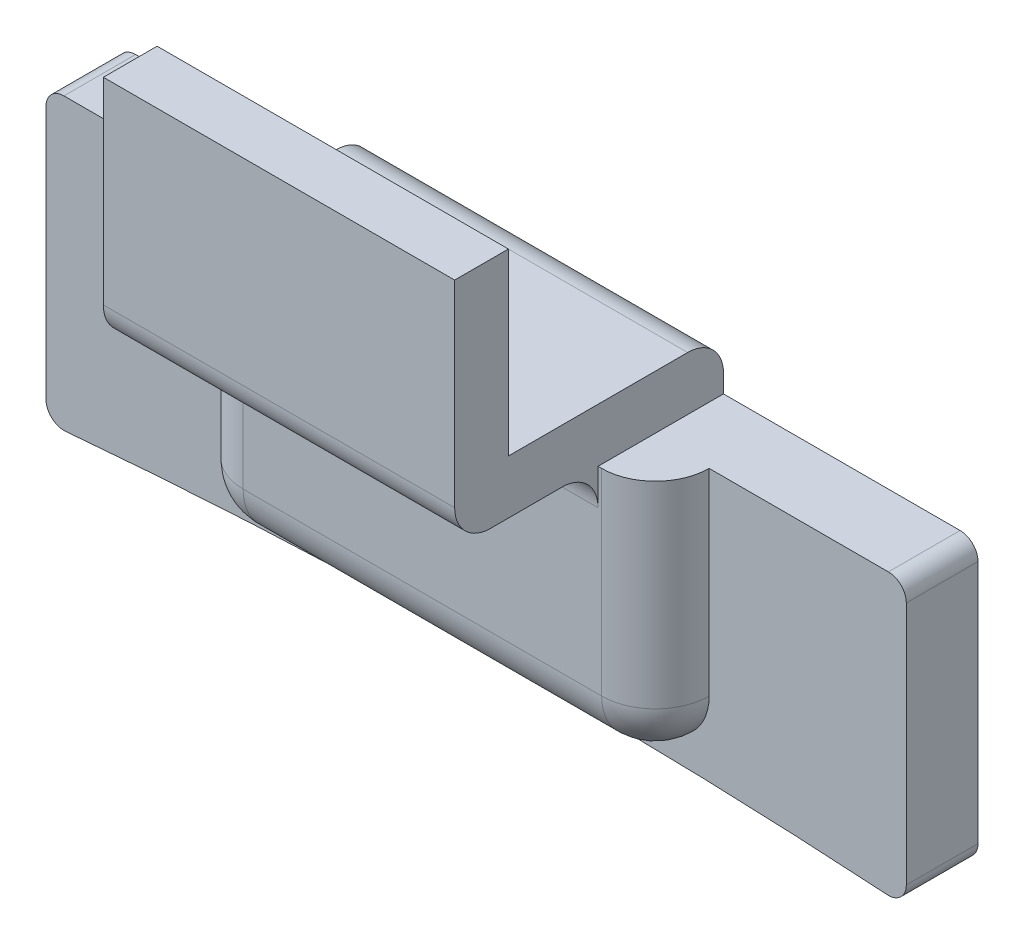
SolidWorks part; units mm, degrees
material "7079 Alloy"
ref_plane "Front Plane" through (0, 0, 0) normal (0, 0, 1) x (1, 0, 0)
ref_plane "Top Plane" through (0, 0, 0) normal (0, 1, 0) x (1, 0, 0)
ref_plane "Right Plane" through (0, 0, 0) normal (1, 0, 0) x (0, 0, -1)
ref_plane "Plane1" through (0, 0, 0) normal (0, 0, -1) x (-1, 0, 0)
sketch "Sketch1" plane through (0, 0, 0) normal (0, 0, -1) x (-1, 0, 0)
  line L0 (27.5, -16.2631) -> (27.5, 0)
  line L1 (27.5, 0) -> (-20.5, 0)
  line L2 (-20.5, 0) -> (-20.5, -15.7012)
  arc A0 (-20.5, -15.7012) -> (27.5, -16.2631) centre (0, -315) cw
  dimension "D1" = 300
  dimension "D2" = 48
extrude "Boss-Extrude1" add sketch "Sketch1" against normal blind 4
sketch "Sketch4" plane through (0, 0, 4) normal (0, 0, 1) x (1, 0, 0)
  line L0 (9.5, 0) -> (9.5, -14)
  line L1 (9.5, -14) -> (-16.5, -14)
  line L2 (-16.5, -14) -> (-16.5, 0)
  line L3 (-16.5, 0) -> (9.5, 0)
  line L5 (20.5, 0) -> (20.5, -15.7012) construction
  dimension "D1" = 26
  dimension "D2" = 11
extrude "Boss-Extrude2" add sketch "Sketch4" along normal blind 3
fillet "Fillet1" radius 1 4 edges at (20.5, 0, 2) (-27.5, 0, 2) (20.5, -15.7012, 2) (-27.5, -16.2631, 2) tangent propagation no
fillet "Fillet3" radius 3 3 edges at (-3.5, -14, 7) (-16.5, -7, 7) (9.5, -7, 7)
fillet "Fillet4" radius 3 2 edges at (-15.6213, -13.1213, 6.1213) (8.6213, -13.1213, 6.1213)
sketch "Sketch5" plane through (0, 0, 0) normal (0, 1, 0) x (1, 0, 0)
  line L0 (6.3, -7) -> (-13.3, -7)
  line L1 (6.3, -7) -> (6.3, 0)
  line L2 (-13.3, -7) -> (-13.3, 0)
  line L3 (6.3, 0) -> (-13.3, 0)
  line L4 (-26.5, 0) -> (19.5, 0) construction
  line L5 (6.5, -7) -> (-13.5, -7) construction
  point P10 (-3.5, -7)
  point P11 (-3.5, -7)
  dimension "D1" = 19.6
extrude "Boss-Extrude3" add sketch "Sketch5" along normal blind 3
sketch "Sketch8" plane through (0, 0, 7) normal (0, 0, 1) x (1, 0, 0)
  line L1 (6.3, 0) -> (-13.3, 0)
  line L2 (6.3, 0) -> (6.3, 3)
  line L3 (6.3, 3) -> (-13.3, 3)
  line L4 (-13.3, 0) -> (-13.3, 3)
extrude "Boss-Extrude5" add sketch "Sketch8" along normal blind 5
sketch "Sketch9" plane through (0, 0, 0) normal (0, -1, 0) x (1, 0, 0)
  line L0 (-13.3, 12) -> (6.3, 12)
  line L1 (-13.3, 12) -> (-13.3, 15)
  line L2 (6.3, 12) -> (6.3, 15)
  line L3 (-13.3, 15) -> (6.3, 15)
  dimension "D1" = 3
extrude "Boss-Extrude6" add sketch "Sketch9" against normal blind 13
fillet "Fillet5" radius 2 3 edges at (-3.5, 0, 15) (-3.5, 3, 0) (-3.5, 0, 7)
